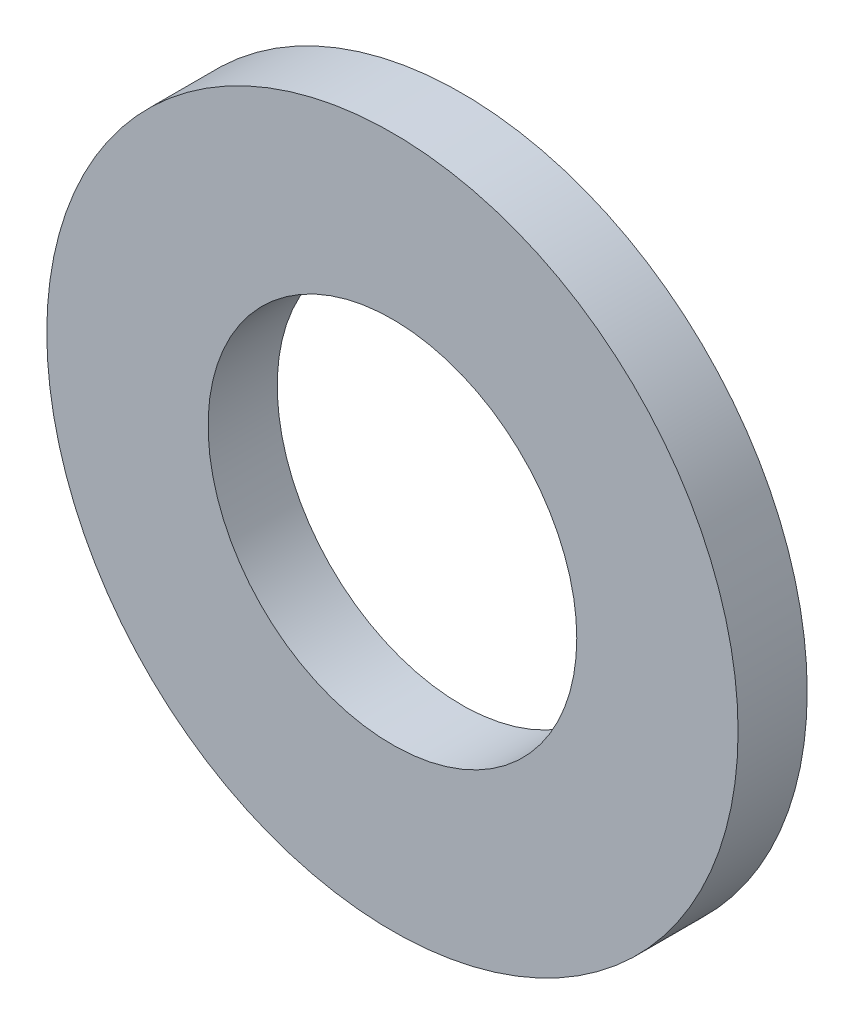
SolidWorks part; units mm, degrees
ref_plane "Front Plane" through (0, 0, 0) normal (0, 0, 1) x (1, 0, 0)
ref_plane "Top Plane" through (0, 0, 0) normal (0, 1, 0) x (1, 0, 0)
ref_plane "Right Plane" through (0, 0, 0) normal (1, 0, 0) x (0, 0, -1)
sketch "Sketch1" plane through (0, 0, 0) normal (0, 0, 1) x (1, 0, 0)
  circle A0 centre (0, 0) radius 3
  circle A1 centre (0, 0) radius 1.6
  dimension "OD" = 6
  dimension "ID1" = 3.2
extrude "Boss-Extrude1" add sketch "Sketch1" along normal blind 0.6
ref_axis "Center Axis 1" through (0, 0, 0.6) along (0, 0, -1)
ref_plane "Contact Plane 1" through (0, 0, 0.6) normal (0, 0, 1) x (1, 0, 0)
ref_plane "Contact Plane 2" through (0, 0, 0) normal (0, 0, -1) x (-1, 0, 0)
